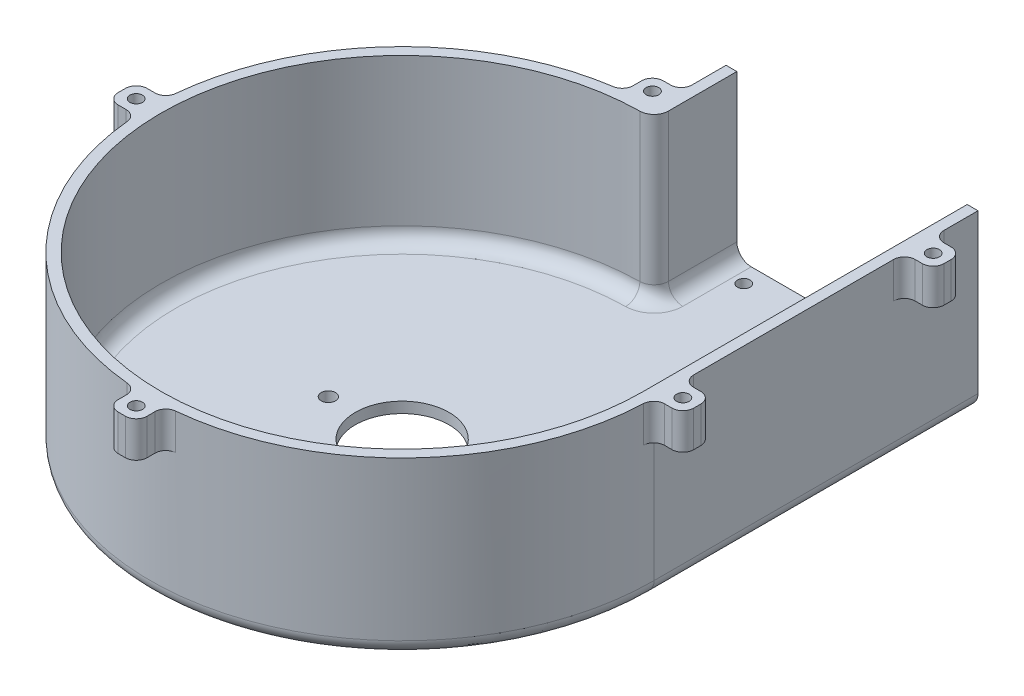
SolidWorks part; units mm, degrees
ref_plane "Front Plane" through (0, 0, 0) normal (0, 0, 1) x (1, 0, 0)
ref_plane "Top Plane" through (0, 0, 0) normal (0, 1, 0) x (1, 0, 0)
ref_plane "Right Plane" through (0, 0, 0) normal (1, 0, 0) x (0, 0, -1)
sketch "Sketch2" plane through (0, 0, 0) normal (0, 1, 0) x (1, 0, 0)
  line L0 (0, 70) -> (70, 70) construction
  line L2 (70, 0) -> (70, 90)
  line L3 (70, 90) -> (0, 90)
  line L4 (0, 70) -> (0, 90)
  circle A0 centre (0, 0) radius 59 construction
  arc A1 (0, 70) -> (70, 0) centre (0, 0) ccw
  circle A2 centre (0, 0) radius 20.5 construction
  circle A3 centre (20.5, 0) radius 2
  circle A4 centre (-20.5, 0) radius 2
  circle A5 centre (0, 0) radius 13
  dimension "D1" = 118
  dimension "D2" = 70
  dimension "D4" = 4
  dimension "D6" = 26
  dimension "D5" = 41
  dimension "D7" = 20
extrude "Boss-Extrude1" add sketch "Sketch2" along normal blind 3
sketch "Sketch3" plane through (0, 3, 0) normal (0, 1, 0) x (1, 0, 0)
  line L3 (70, 90) -> (0, 90) construction
  line L4 (0, 90) -> (3, 90)
  line L5 (67, 90) -> (70, 90)
  line L6 (67, 0) -> (67, 87)
  line L7 (67, 87) -> (3, 87)
  line L8 (3, 87) -> (3, 66.9328)
  line L9 (67, 0) -> (67, 90)
  line L11 (3, 90) -> (3, 66.9328)
  line L12 (70, 0) -> (70, 90)
  line L13 (70, 90) -> (0, 90)
  line L14 (0, 90) -> (0, 70)
  line L15 (70, 0) -> (70, 90)
  line L17 (0, 90) -> (0, 70)
  arc A2 (3, 66.9328) -> (67, 0) centre (0, 0) ccw
  arc A3 (3, 66.9328) -> (67, 0) centre (0, 0) ccw
  arc A4 (0, 70) -> (70, 0) centre (0, 0) ccw
  arc A5 (0, 70) -> (70, 0) centre (0, 0) ccw
  dimension "D1" = 3
  dimension "D2" = 0
extrude "Boss-Extrude2" add sketch "Sketch3" along normal blind 45
sketch "Sketch4" plane through (0, 48, 0) normal (0, 1, 0) x (1, 0, 0)
  line L0 (-4, 77.5414) -> (-4, 69.5414) construction
  line L1 (0, 77.5414) -> (-8, 77.5414)
  line L2 (0, 77.5414) -> (0, 70)
  line L4 (-8, 77.5414) -> (-8, 69.5414)
  line L5 (70, 77.5414) -> (78, 77.5414)
  line L6 (70, 77.5414) -> (70, 69.5414)
  line L7 (70, 69.5414) -> (78, 69.5414)
  line L8 (78, 77.5414) -> (78, 69.5414)
  line L9 (74, 77.5414) -> (74, 69.5414) construction
  line L10 (0, 70) -> (0, 69.5414) construction
  line L11 (0, 69.5414) -> (-8, 69.5414) construction
  line L13 (70, 0) -> (70, 90) construction
  line L14 (-77.8856, 0) -> (-69.8856, 0) construction
  line L15 (-69.8856, 4) -> (-77.8856, 4)
  line L16 (-69.8856, 4) -> (-69.8856, -4)
  line L17 (-69.8856, -4) -> (-77.8856, -4)
  line L18 (-77.8856, 4) -> (-77.8856, -4)
  line L19 (0, -69.8856) -> (0, -77.8856) construction
  line L20 (-4, -69.8856) -> (4, -69.8856)
  line L21 (-4, -69.8856) -> (-4, -77.8856)
  line L22 (-4, -77.8856) -> (4, -77.8856)
  line L23 (4, -69.8856) -> (4, -77.8856)
  line L24 (78, 4) -> (70, 4) construction
  line L25 (70, 0) -> (78, 0)
  line L26 (70, 0) -> (70, 8)
  line L27 (70, 8) -> (78, 8)
  line L28 (78, 0) -> (78, 8)
  circle A0 centre (-4, 73.5414) radius 1.75
  circle A1 centre (74, 73.5414) radius 1.75
  arc A2 (0, 70) -> (70, 0) centre (0, 0) ccw construction
  circle A3 centre (-73.8856, 0) radius 1.75
  circle A4 centre (0, -73.8856) radius 1.75
  circle A5 centre (74, 4) radius 1.75
  arc M8 (0, 70) -> (70, 0) centre (0, 0) ccw
  line M9 (70, 0) -> (70, 90)
  line M15 (0, 90) -> (0, 70)
  dimension "D5" = 3.5
  dimension "D6" = 3.5
  dimension "D8" = 3.5
  dimension "D10" = 3.5
  dimension "D12" = 3.5
  dimension "D1" = 8
  dimension "D2" = 8
  dimension "D3" = 8
  dimension "D4" = 8
  dimension "D7" = 8
  dimension "D9" = 8
  dimension "D11" = 8
extrude "Boss-Extrude3" add sketch "Sketch4" against normal blind 10 contours L23 L21 L22 A4 M8 | L15 L18 L17 A3 M8 | L25 L28 L27 A5 M9 | L8 L5 L7 A1 M9 | L1 L4 A0 M8 M15 region at (-0.1131, 48, -73.7707) region at (70.1131, 48, -73.5414) region at (70.1131, 48, -4) region at (0, 48, 70.1131) region at (-70.1131, 48, 0)
fillet "Fillet1" radius 3 19 edges at (70, 43, -77.5414) (78, 43, -77.5414) (78, 43, -69.5414) (70, 43, -69.5414) (70, 43, -8) (78, 43, -8) (78, 43, 0) (70, 43, 0) (4, 43, 69.8856) (4, 43, 77.8856) (-4, 43, 77.8856) (-4, 43, 69.8856) (-69.8856, 43, 4) (-77.8856, 43, 4) (-77.8856, 43, -4) (-69.8856, 43, -4) (-8, 43, -69.5414) (0, 43, -77.5414) (-8, 43, -77.5414)
fillet "Fillet2" radius 4 1 edges at (3, 25.5, -66.9328)
fillet "Fillet3" radius 4 4 edges at (67, 3, -45) (3, 3, -80.4965) (1.8483, 3, -68.1845) (-47.0413, 3, 47.7086)
fillet "Fillet4" radius 4 4 edges at (-49.4975, 0, 49.4975) (70, 0, -45) (0, 19, -70) (0, 0, -80)
sketch "Sketch5" plane through (0, 0, 0) normal (0, -1, 0) x (1, 0, 0)
  line L0 (0, -84.93) -> (70, -84.93) construction
  line L1 (0, -90) -> (0, -73.8918) construction
  line L2 (70, 0) -> (70, -90) construction
  line L3 (66, -90) -> (4, -90) construction
  circle A0 centre (10, -84.93) radius 1.75
  circle A1 centre (60, -84.93) radius 1.75
  dimension "D2" = 3.5
  dimension "D3" = 3.5
  dimension "D1" = 5.07
  dimension "D4" = 10
  dimension "D5" = 10
extrude "Cut-Extrude1" cut sketch "Sketch5" against normal through all
